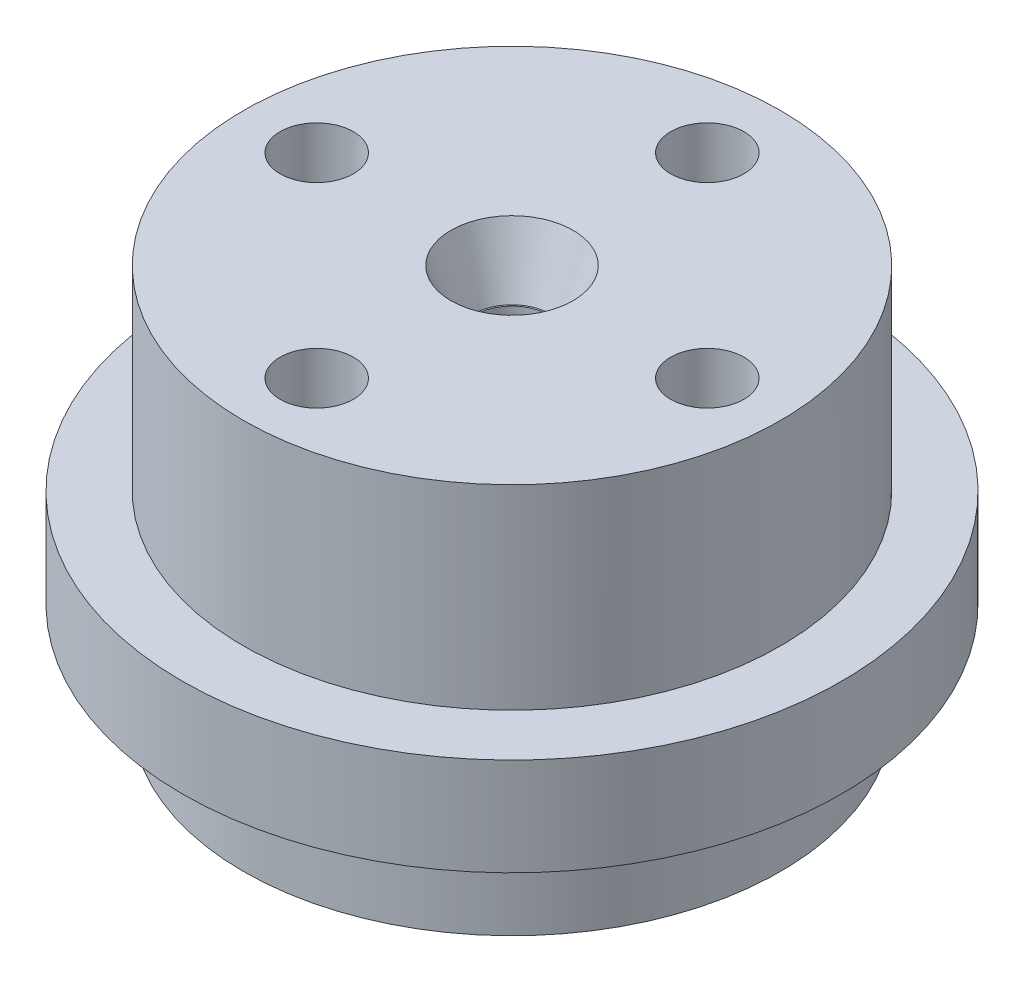
SolidWorks part; units mm, degrees
ref_plane "Front Plane" through (0, 0, 0) normal (0, 0, 1) x (1, 0, 0)
ref_plane "Top Plane" through (0, 0, 0) normal (0, 1, 0) x (1, 0, 0)
ref_plane "Right Plane" through (0, 0, 0) normal (1, 0, 0) x (0, 0, -1)
sketch "Sketch1" plane through (0, 0, 0) normal (0, 1, 0) x (1, 0, 0)
  circle A0 centre (0, 0) radius 11
extrude "Boss-Extrude1" add sketch "Sketch1" along normal blind 16
sketch "Sketch2" plane through (0, 16, 0) normal (0, 1, 0) x (1, 0, 0)
  circle A0 centre (0, 0) radius 1.5
extrude "Cut-Extrude1" cut sketch "Sketch2" against normal through all
sketch "Sketch3" plane through (0, 16, 0) normal (0, 1, 0) x (1, 0, 0)
  circle A0 centre (0, 0) radius 2.5
extrude "Cut-Extrude2" cut sketch "Sketch3" against normal blind 2.5 draft 20.5
ref_plane "Plane1" through (0, 6, 0) normal (0, -1, 0) x (-1, 0, 0)
sketch "Sketch5" plane through (0, 6, 0) normal (0, -1, 0) x (-1, 0, 0)
  circle A0 centre (0, 0) radius 13.5
extrude "Boss-Extrude2" add sketch "Sketch5" along normal blind 2 and the other way blind 2
sketch "Sketch7" plane through (0, 16, 0) normal (0, 1, 0) x (1, 0, 0)
  circle A0 centre (0, 8) radius 1.5
  circle A1 centre (8, 0) radius 1.5
  circle A2 centre (0, -8) radius 1.5
  circle A3 centre (-8, 0) radius 1.5
  point P12 (0, 0)
  dimension "D1" = 8
  dimension "D2" = 4
extrude "Cut-Extrude3" cut sketch "Sketch7" against normal through all
